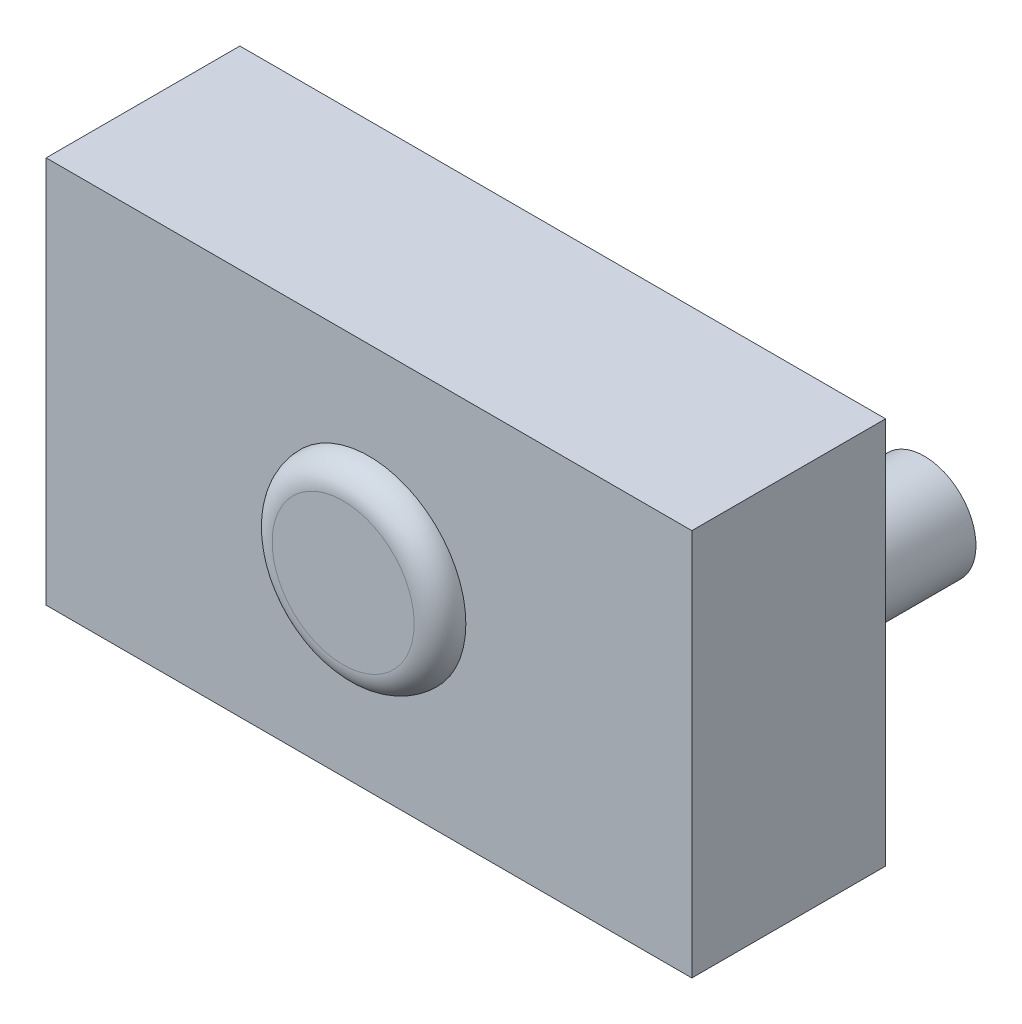
SolidWorks part; units mm, degrees
ref_plane "Front" through (0, 0, 0) normal (0, 0, 1) x (1, 0, 0)
ref_plane "Top" through (0, 0, 0) normal (0, 1, 0) x (1, 0, 0)
ref_plane "Right" through (0, 0, 0) normal (1, 0, 0) x (0, 0, -1)
sketch "Sketch1" plane through (0, 0, 0) normal (0, 0, 1) x (1, 0, 0)
  line L1 (-25, -15) -> (25, -15)
  line L2 (-25, -15) -> (-25, 15)
  line L3 (-25, 15) -> (25, 15)
  line L4 (25, -15) -> (25, 15)
  line L5 (0, 15) -> (0, -15) construction
  line L6 (-25, 0) -> (25, 0) construction
  point P0 (0, 0)
  dimension "D1" = 50
  dimension "D2" = 30
extrude "Boss-Extrude1" add sketch "Sketch1" along normal blind 15
sketch "Sketch2" plane through (0, 0, 0) normal (0, 0, -1) x (-1, 0, 0)
  line L0 (-25, -15) -> (-25, 15) construction
  line L1 (25, 15) -> (25, -15) construction
  circle A0 centre (-18, 0) radius 4
  circle A1 centre (18, 0) radius 4
  point P4 (0, 0)
  dimension "D1" = 8
  dimension "D2" = 7
  dimension "D3" = 7
extrude "Boss-Extrude2" add sketch "Sketch2" along normal blind 10
sketch "Sketch3" plane through (0, 0, 15) normal (0, 0, 1) x (1, 0, 0)
  circle A0 centre (0, 0) radius 7.5
  dimension "D1" = 15
extrude "Boss-Extrude3" add sketch "Sketch3" along normal blind 2
fillet "Fillet1" radius 2 1 edges at (7.5, 0, 17)
